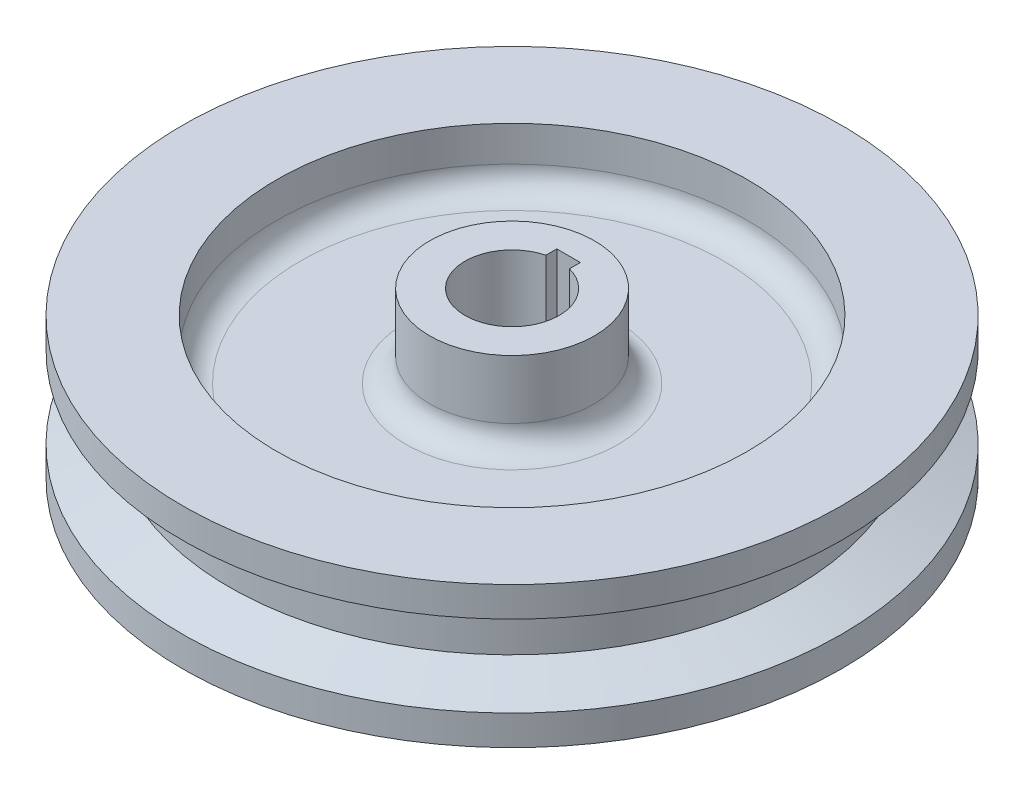
SolidWorks part; units mm, degrees
material "Cast Stainless Steel"
ref_plane "Front Plane" through (0, 0, 0) normal (0, 0, 1) x (1, 0, 0)
ref_plane "Top Plane" through (0, 0, 0) normal (0, 1, 0) x (1, 0, 0)
ref_plane "Right Plane" through (0, 0, 0) normal (1, 0, 0) x (0, 0, -1)
sketch "Sketch1" plane through (0, 0, 0) normal (0, 0, 1) x (1, 0, 0)
  line L0 (0, -1000) -> (0, 49000) construction
  line L1 (-1000, 0) -> (49000, 0) construction
  line L2 (12.7, 25.4) -> (22.225, 25.4)
  line L3 (22.225, 25.4) -> (22.225, 9.525)
  line L4 (28.575, 3.175) -> (57.15, 3.175)
  line L5 (63.5, 9.525) -> (63.5, 19.05)
  line L6 (63.5, 19.05) -> (88.9, 19.05)
  line L7 (88.9, 19.05) -> (88.9, 10.9724)
  line L8 (88.9, 10.9724) -> (76.2, 6.35)
  line L9 (76.2, 6.35) -> (76.2, -6.35)
  line L10 (88.9, -10.9724) -> (76.2, -6.35)
  line L11 (88.9, -19.05) -> (88.9, -10.9724)
  line L12 (63.5, -19.05) -> (88.9, -19.05)
  line L13 (63.5, -9.525) -> (63.5, -19.05)
  line L14 (28.575, -3.175) -> (57.15, -3.175)
  line L15 (22.225, -25.4) -> (22.225, -9.525)
  line L16 (12.7, -25.4) -> (22.225, -25.4)
  line L17 (12.7, 25.4) -> (12.7, -25.4)
  arc A0 (63.5, 9.525) -> (57.15, 3.175) centre (57.15, 9.525) cw
  arc A1 (28.575, 3.175) -> (22.225, 9.525) centre (28.575, 9.525) cw
  arc A2 (28.575, -3.175) -> (22.225, -9.525) centre (28.575, -9.525) ccw
  arc A3 (63.5, -9.525) -> (57.15, -3.175) centre (57.15, -9.525) ccw
  point P27 (76.2, 0)
  dimension "D9" = 6.35
  dimension "D1" = 177.8
  dimension "D2" = 44.45
  dimension "D3" = 6.35
  dimension "D4" = 38.1
  dimension "D5" = 50.8
  dimension "D6" = 6.35
  dimension "D7" = 12.7
  dimension "D8" = 20
  dimension "D10" = 127
  dimension "D11" = 25.4
revolve "Revolve1" add sketch "Sketch1" angle 360 about L0
sketch "Sketch2" plane through (0, 25.4, 0) normal (0, 1, 0) x (1, 0, 0)
  line L0 (-201000, 0) -> (249000, 0) construction
  line L1 (3.175, 0) -> (-3.175, 0)
  line L2 (3.175, 0) -> (3.175, 15.24)
  line L3 (3.175, 15.24) -> (-3.175, 15.24)
  line L4 (-3.175, 0) -> (-3.175, 15.24)
  line L5 (3.175, 0) -> (-3.175, 15.24) construction
  line L6 (3.175, 15.24) -> (-3.175, 0) construction
  line L7 (-201000, 0) -> (249000, 0) construction
  point P0 (0, 7.62)
  dimension "D1" = 15.24
  dimension "D2" = 6.35
extrude "Cut-Extrude1" cut sketch "Sketch2" against normal up to surface (50.8 mm away) up to face at (22.225, -25.4, 0)
